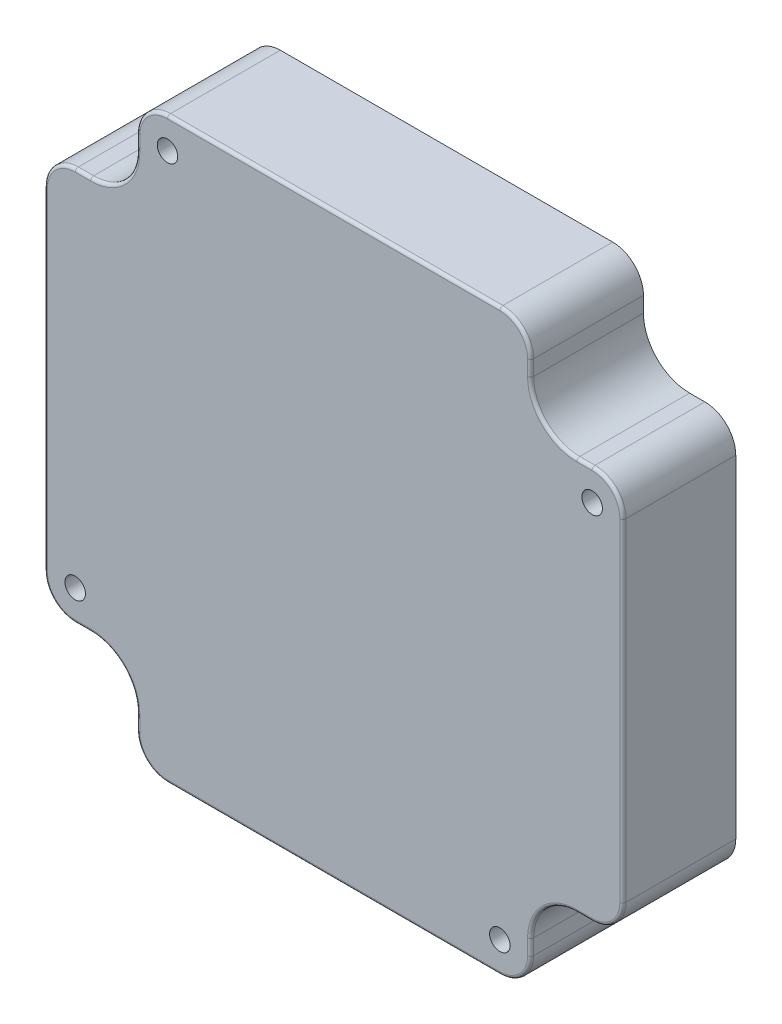
SolidWorks part; units mm, degrees
material "1060 Alloy"
ref_plane "Front Plane" through (0, 0, 0) normal (0, 0, 1) x (1, 0, 0)
ref_plane "Top Plane" through (0, 0, 0) normal (0, 1, 0) x (1, 0, 0)
ref_plane "Right Plane" through (0, 0, 0) normal (1, 0, 0) x (0, 0, -1)
sketch "Sketch1" plane through (0, 0, 0) normal (0, 0, 1) x (1, 0, 0)
  line L0 (0, 28.2) -> (0, -28.2) construction
  line L1 (-28.2, 28.2) -> (28.2, 28.2) construction
  line L2 (-28.2, 28.2) -> (-28.2, -28.2) construction
  line L3 (-28.2, -28.2) -> (28.2, -28.2) construction
  line L4 (28.2, 28.2) -> (28.2, -28.2) construction
  line L5 (-28.2, 28.2) -> (28.2, -28.2) construction
  line L6 (-28.2, -28.2) -> (28.2, 28.2) construction
  line L7 (-23.7, 23.7) -> (23.7, 23.7) construction
  line L8 (-23.7, 23.7) -> (-23.7, -23.7) construction
  line L9 (-23.7, -23.7) -> (23.7, -23.7) construction
  line L10 (23.7, 23.7) -> (23.7, -23.7) construction
  line L11 (-23.7, 23.7) -> (23.7, -23.7) construction
  line L12 (-23.7, -23.7) -> (23.7, 23.7) construction
  line L13 (-28.2, 0) -> (28.2, 0) construction
  line L14 (-23.7, 19.2) -> (-25.1852, 19.2)
  line L15 (-19.2, 23.7) -> (-19.2, 25.2)
  line L16 (16.2, -28.2) -> (-16.2, -28.2)
  line L17 (-28.2, -16.2) -> (-28.2, 16.2)
  line L18 (19.2, 23.7) -> (19.2, 25.2)
  line L19 (23.7, 19.2) -> (25.1852, 19.2)
  line L20 (28.2, 16.2) -> (28.2, -16.2)
  line L21 (16.2, 28.2) -> (-16.2, 28.2)
  line L23 (-23.7, -19.2) -> (-25.1852, -19.2)
  line L24 (-19.2, -23.7) -> (-19.2, -25.2)
  line L27 (23.7, -19.2) -> (25.1852, -19.2)
  line L28 (19.2, -23.7) -> (19.2, -25.2)
  arc A1 (-16.2, 28.2) -> (-19.2, 25.2) centre (-16.2, 25.2) ccw
  arc A2 (-28.2, 16.2) -> (-25.1852, 19.2) centre (-25.2, 16.2) cw
  arc A3 (-23.7, 19.2) -> (-19.2, 23.7) centre (-23.7, 23.7) ccw
  arc A4 (23.7, 19.2) -> (19.2, 23.7) centre (23.7, 23.7) cw
  arc A5 (28.2, 16.2) -> (25.1852, 19.2) centre (25.2, 16.2) ccw
  circle A6 centre (-16.2, 25.2) radius 1
  arc A7 (16.2, 28.2) -> (19.2, 25.2) centre (16.2, 25.2) cw
  circle A8 centre (-25.2, -16.2) radius 1
  arc A9 (-28.2, -16.2) -> (-25.1852, -19.2) centre (-25.2, -16.2) ccw
  arc A10 (-23.7, -19.2) -> (-19.2, -23.7) centre (-23.7, -23.7) cw
  arc A11 (-16.2, -28.2) -> (-19.2, -25.2) centre (-16.2, -25.2) cw
  circle A12 centre (16.2, -25.2) radius 1
  arc A13 (28.2, -16.2) -> (25.1852, -19.2) centre (25.2, -16.2) cw
  arc A14 (23.7, -19.2) -> (19.2, -23.7) centre (23.7, -23.7) ccw
  arc A15 (16.2, -28.2) -> (19.2, -25.2) centre (16.2, -25.2) ccw
  circle A16 centre (25.2, 16.2) radius 1
  point P0 (0, 0)
  point P6 (0, 0)
  dimension "D1" = 56.4
  dimension "D2" = 47.4
extrude "Boss-Extrude1" add sketch "Sketch1" along normal blind 11
sketch "Sketch2" plane through (0, 0, 0) normal (0, 0, 1) x (1, 0, 0)
  line L0 (-16.2, -28.2) -> (16.2, -28.2) construction
  line L1 (-10.811, -26.1) -> (10.811, -26.1)
  line L2 (10.811, -26.1) -> (26.1, -10.811)
  line L3 (26.1, -10.811) -> (26.1, 10.811)
  line L4 (26.1, 10.811) -> (10.811, 26.1)
  line L5 (10.811, 26.1) -> (-10.811, 26.1)
  line L6 (-10.811, 26.1) -> (-26.1, 10.811)
  line L7 (-26.1, 10.811) -> (-26.1, -10.811)
  line L8 (-26.1, -10.811) -> (-10.811, -26.1)
  circle A0 centre (0, 0) radius 26.1 construction
  circle A1 centre (0, 0) radius 20
  dimension "D1" = 52.2
  dimension "D2" = 40
extrude "Cut-Extrude1" cut sketch "Sketch2" along normal blind 8.5
sketch "Sketch3" plane through (0, 0, 0) normal (0, 0, -1) x (-1, 0, 0)
  circle A0 centre (0, 0) radius 16
  circle A1 centre (0, 0) radius 18
  dimension "D1" = 36
extrude "Cut-Extrude2" cut sketch "Sketch3" against normal blind 10
fillet "Fillet1" radius 0.3 24 edges at (27.3161, -18.3266, 11) (24.4426, -19.2, 11) (20.518, -20.518, 11) (19.2, -24.45, 11) (18.3213, -27.3213, 11) (0, -28.2, 11) (-18.3213, -27.3213, 11) (-19.2, -24.45, 11) (-20.518, -20.518, 11) (-24.4426, -19.2, 11) (-27.3161, -18.3266, 11) (-28.2, 0, 11) (-27.3161, 18.3266, 11) (-24.4426, 19.2, 11) (-20.518, 20.518, 11) (-19.2, 24.45, 11) (-18.3213, 27.3213, 11) (0, 28.2, 11) (18.3213, 27.3213, 11) (19.2, 24.45, 11) (20.518, 20.518, 11) (24.4426, 19.2, 11) (27.3161, 18.3266, 11) (28.2, 0, 11)
sketch "Sketch4" plane through (-28.2, 0, 0) normal (-1, 0, 0) x (0, 0, 1)
  line L0 (0, 0) -> (11, 0) construction
  line L1 (11, 16.2) -> (11, -16.2) construction
  line L2 (0, 16.2) -> (0, -16.2) construction
  line L3 (5.5, 4) -> (0, 4) construction
  line L4 (5.5, 4) -> (5.5, -4) construction
  line L5 (5.5, -4) -> (0, -4) construction
  line L6 (0, 4) -> (0, -4) construction
  line L8 (0, 4) -> (5.5, 4)
  line L9 (0, 4) -> (0, -4)
  line L10 (0, -4) -> (5.5, -4)
  circle A0 centre (5.5, 0) radius 4 construction
  arc A1 (5.5, -4) -> (5.5, 4) centre (5.5, 0) ccw
  dimension "D1" = 8
